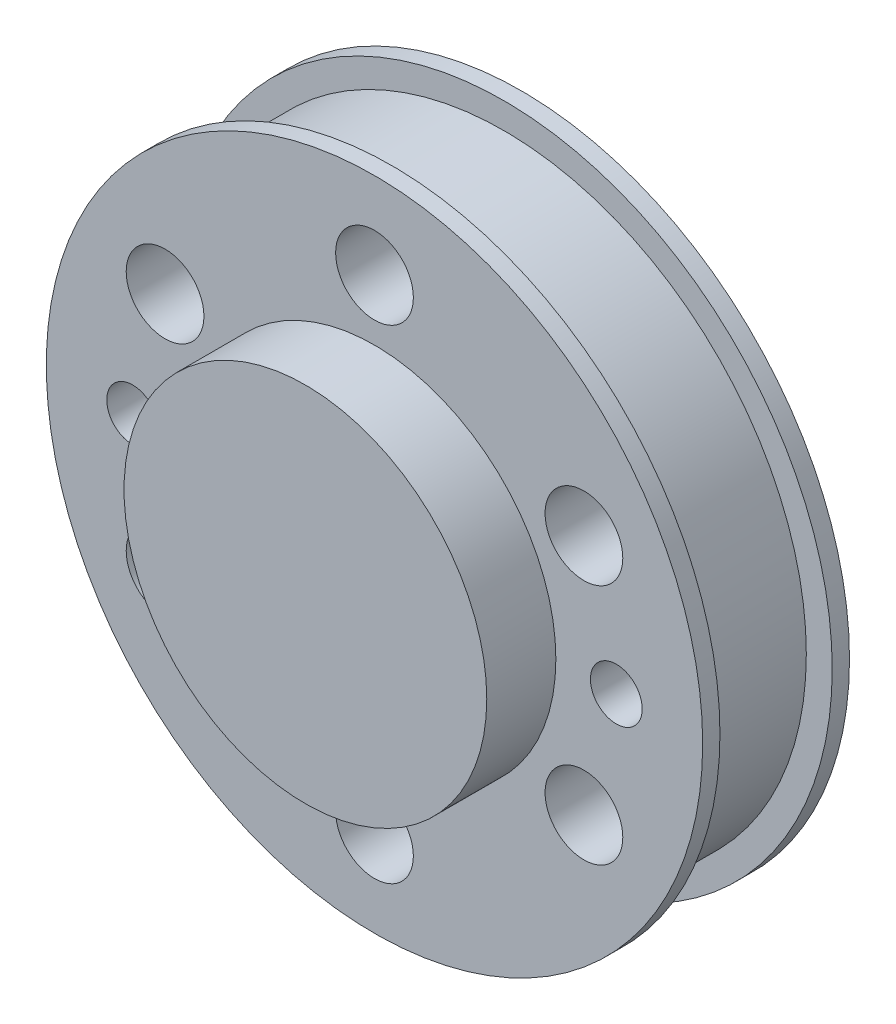
SolidWorks part; units mm, degrees
material "PA Type 6"
ref_plane "Front Plane" through (0, 0, 0) normal (0, 0, 1) x (1, 0, 0)
ref_plane "Top Plane" through (0, 0, 0) normal (0, 1, 0) x (1, 0, 0)
ref_plane "Right Plane" through (0, 0, 0) normal (1, 0, 0) x (0, 0, -1)
sketch "Sketch1" plane through (0, 0, 0) normal (0, 1, 0) x (1, 0, 0)
  line L0 (19, 8.5) -> (19, 7.5)
  line L1 (19, 7.5) -> (17.5, 7.5)
  line L2 (17.5, 7.5) -> (17.5, 1)
  line L3 (17.5, 1) -> (19, 1)
  line L4 (19, 1) -> (19, 0)
  line L5 (19, 0) -> (10.5, 0)
  line L6 (10.5, 0) -> (10.5, -4)
  line L7 (10.5, -4) -> (0, -4)
  line L8 (0, -4) -> (0, 8.5)
  line L9 (0, 8.5) -> (19, 8.5)
  dimension "D1" = 10.5
  dimension "D2" = 4
  dimension "D3" = 17.5
  dimension "D4" = 1.5
  dimension "D5" = 6.5
  dimension "D6" = 1
revolve "Revolve1" add sketch "Sketch1" angle 360 about L8
sketch "Sketch4" plane through (0, 0, -8.5) normal (0, 0, -1) x (-1, 0, 0)
  circle A0 centre (0, 0) radius 14
  point P5 (0, 14)
  point P11 (12.1244, 7)
  point P12 (12.1244, -7)
  point P13 (0, -14)
  point P14 (-12.1244, -7)
  point P15 (-12.1244, 7)
  dimension "D1" = 28
  dimension "D2" = 6
hole_wizard "M4 Clearance Hole1" positions "Sketch4" profile "Sketch5" hole size "M4" standard "DIN" end condition through all
sketch "Sketch5" plane through (12.1244, 7, -8.5) normal (1, 0, 0) x (0, 1, 0)
  line L0 (0, 0) -> (0, 12.5)
  line L1 (0, 12.5) -> (2.25, 12.5)
  line L2 (2.25, 12.5) -> (2.25, 0)
  line L5 (2.25, 0) -> (0, 0)
  line L11 (0, -6.35) -> (0, 107.95) construction
  dimension "Thru Hole Dia." = 4.5
  dimension "Thru Hole Depth" = 12.5
sketch "Sketch8" plane through (0, 0, -8.5) normal (0, 0, -1) x (-1, 0, 0)
  circle A0 centre (0, 0) radius 14
  point P6 (-14, 0)
  point P8 (14, 0)
hole_wizard "Ø3.0mm Dowel Hole1" positions "Sketch8" profile "Sketch7" hole size "Ø3.0" standard "DIN" end condition through all
sketch "Sketch7" plane through (-14, 0, -8.5) normal (1, 0, 0) x (0, 1, 0)
  line L0 (0, 0) -> (0, 12.5)
  line L1 (0, 12.5) -> (1.5, 12.5)
  line L2 (1.5, 12.5) -> (1.5, 0)
  line L5 (1.5, 0) -> (0, 0)
  line L11 (0, -6.35) -> (0, 107.95) construction
  dimension "Thru Hole Dia." = 3
  dimension "Thru Hole Depth" = 12.5
